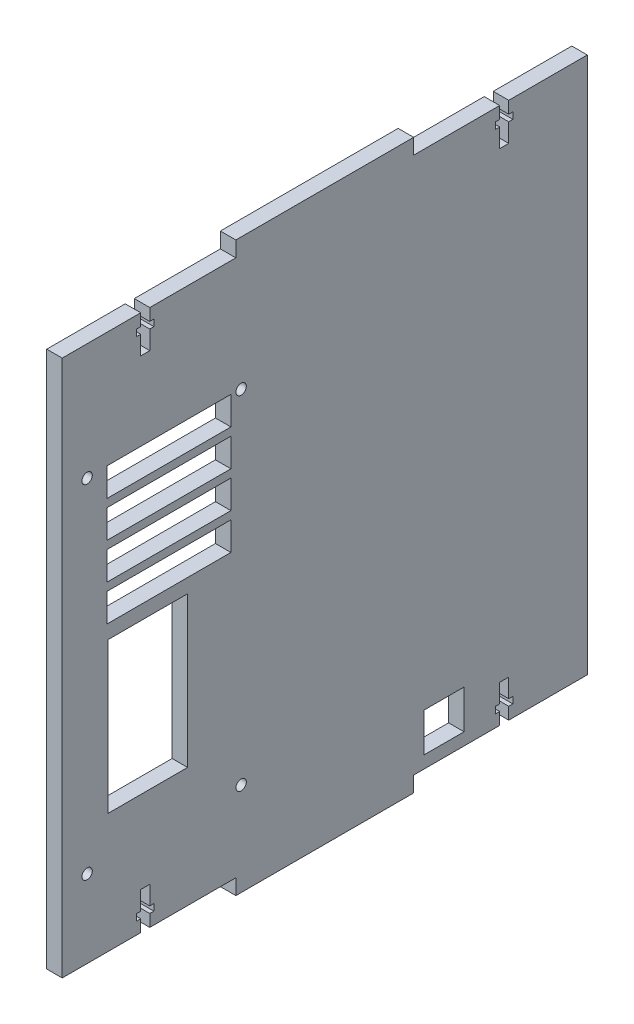
SolidWorks part; units mm, degrees
ref_plane "Front Plane" through (0, 0, 0) normal (0, 0, 1) x (1, 0, 0)
ref_plane "Top Plane" through (0, 0, 0) normal (0, 1, 0) x (1, 0, 0)
ref_plane "Right Plane" through (0, 0, 0) normal (1, 0, 0) x (0, 0, -1)
sketch "Sketch1" plane through (0, 0, 0) normal (1, 0, 0) x (0, 0, -1)
  line L1 (-35.6928, 37.9569) -> (138.1972, 37.9569)
  line L2 (-35.6928, 37.9569) -> (-35.6928, -139.8431)
  line L3 (-35.6928, -139.8431) -> (138.1972, -139.8431)
  line L4 (138.1972, 37.9569) -> (138.1972, -139.8431)
  dimension "D1" = 173.89
  dimension "D2" = 177.8
extrude "Boss-Extrude1" add sketch "Sketch1" along normal blind 5.13
sketch "Sketch6" plane through (0, 37.9569, 0) normal (0, 1, 0) x (1, 0, 0)
  line L0 (5.13, 138.1972) -> (5.13, -35.6928) construction
  line L1 (5.13, 21.8122) -> (0, 21.8122)
  line L2 (5.13, 21.8122) -> (5.13, 80.6922)
  line L3 (5.13, 80.6922) -> (0, 80.6922)
  line L4 (0, 21.8122) -> (0, 80.6922)
  line L5 (0, 138.1972) -> (0, -35.6928) construction
  line L6 (5.13, -35.6928) -> (0, -35.6928) construction
  point P10 (5.13, 51.2522)
  point P11 (2.565, -35.6928)
  dimension "D1" = 86.945
  dimension "D2" = 58.88
extrude "teeth" add sketch "Sketch6" along normal blind 5.13
ref_axis "Axis1" through (0, -50.9431, 35.6928) along (0, 0, -1)
ref_axis "Axis2" through (5.13, 43.0869, -51.2522) along (0, 1, 0)
sketch "Sketch2" plane through (5.13, 0, 0) normal (1, 0, 0) x (0, 0, -1)
  line L0 (-9.6878, 37.9569) -> (-6.6908, 37.9569)
  line L1 (138.1972, 37.9569) -> (80.6922, 37.9569) construction
  line L2 (-6.6908, 37.9569) -> (-6.6908, 33.9619)
  line L3 (-6.6908, 33.9619) -> (-5.3318, 33.9619)
  line L4 (-5.3318, 33.9619) -> (-5.3318, 31.7949)
  line L5 (-5.3318, 31.7949) -> (-6.6908, 31.7949)
  line L6 (-6.6908, 31.7949) -> (-6.6908, 25.5879)
  line L7 (-6.6908, 25.5879) -> (-9.6878, 25.5879)
  line L8 (-9.6878, 25.5879) -> (-9.6878, 31.7949)
  line L9 (-9.6878, 31.7949) -> (-11.0468, 31.7949)
  line L10 (-11.0468, 31.7949) -> (-11.0468, 33.9619)
  line L11 (-11.0468, 33.9619) -> (-9.6878, 33.9619)
  line L12 (-9.6878, 33.9619) -> (-9.6878, 37.9569)
  line L25 (-35.6928, -50.9431) -> (138.1972, -50.9431) construction
  line L26 (-35.6928, 37.9569) -> (-35.6928, -139.8431) construction
  line L27 (138.1972, -139.8431) -> (138.1972, 37.9569) construction
  dimension "D1" = 2.167
  dimension "D2" = 2.997
  dimension "D3" = 2.997
  dimension "D4" = 3.995
  dimension "D5" = 3.995
  dimension "D6" = 1.359
  dimension "D7" = 1.359
  dimension "D8" = 6.207
  dimension "D9" = 6.207
  dimension "D10" = 1.359
  dimension "D12" = 26.005
extrude "t-slot" cut sketch "Sketch2" against normal blind 5.13
pattern_linear "t-slot pattern" count 2 spacing 118.88 along (0, 0, -1) of "t-slot"
ref_plane "Plane1" through (0, -50.9431, 0) normal (0, -1, 0) x (1, 0, 0)
mirror "t-slot bottom" about plane through (0, -50.9431, 0) normal (0, -1, 0) of "t-slot", "t-slot pattern"
sketch "Sketch3" plane through (5.13, 0, 0) normal (1, 0, 0) x (0, 0, -1)
  line L1 (-20.4844, -50.3894) -> (5.8377, -50.3894)
  line L2 (-20.4844, -50.3894) -> (-20.4844, -100.2155)
  line L3 (-20.4844, -100.2155) -> (5.8377, -100.2155)
  line L4 (5.8377, -50.3894) -> (5.8377, -100.2155)
extrude "power port" cut sketch "Sketch3" against normal blind 5.13
sketch "Sketch7" plane through (5.13, 0, 0) normal (1, 0, 0) x (0, 0, -1)
  circle A0 centre (-27.4428, -0.5931) radius 1.7145
  dimension "D1" = 3.429
  dimension "D3" = 2
extrude "Power supply screws" cut sketch "Sketch7" against normal up to next
sketch "Sketch4" plane through (5.13, 0, 0) normal (1, 0, 0) x (0, 0, -1)
  line L1 (-20.8218, -0.3724) -> (20.1782, -0.3724)
  line L2 (-20.8218, -0.3724) -> (-20.8218, -9.7269)
  line L3 (-20.8218, -9.7269) -> (20.1782, -9.7269)
  line L4 (20.1782, -0.3724) -> (20.1782, -9.7269)
  dimension "D1" = 9.3546
  dimension "D2" = 41
extrude "fan vent" cut sketch "Sketch4" against normal blind 5.13
pattern_linear "LPattern3" count 4 spacing 12 along (0, -1, 0) of "fan vent"
sketch "Sketch5" plane through (5.13, 0, 0) normal (1, 0, 0) x (0, 0, -1)
  line L1 (97.3951, -122.9234) -> (84.0794, -122.9234)
  line L2 (97.3951, -122.9234) -> (97.3951, -135.7661)
  line L3 (97.3951, -135.7661) -> (84.0794, -135.7661)
  line L4 (84.0794, -122.9234) -> (84.0794, -135.7661)
extrude "USB port" cut sketch "Sketch5" against normal blind 5.13
ref_plane "Plane2" [suppressed] through (5.13, -139.8431, -67.6179) normal (0, 0, -1) x (-1, 0, 0)
sketch "Sketch11" plane through (0, -139.8431, 0) normal (0, -1, 0) x (1, 0, 0)
  line L0 (5.13, 6.6908) -> (5.13, -109.1922) construction
  line L1 (5.13, -21.8122) -> (0, -21.8122)
  line L2 (5.13, -21.8122) -> (5.13, -80.6922)
  line L3 (5.13, -80.6922) -> (0, -80.6922)
  line L4 (0, -21.8122) -> (0, -80.6922)
  line L5 (0, 6.6908) -> (0, -109.1922) construction
  line L6 (5.13, 35.6928) -> (0, 35.6928) construction
  point P8 (5.13, -51.2522)
  dimension "D1" = 58.88
  dimension "D2" = 86.945
extrude "Boss-Extrude2" add sketch "Sketch11" along normal blind 5.13
pattern_linear "LPattern4" count 2 spacing 51 along (0, 0, -1) count 2 spacing 113.5 along (0, -1, 0) of "Power supply screws"
equation "\"D1@Sketch6\" = \"D1@Sketch1\"/2"
equation "\"D2@Sketch11\" = \"D1@Sketch6\""
